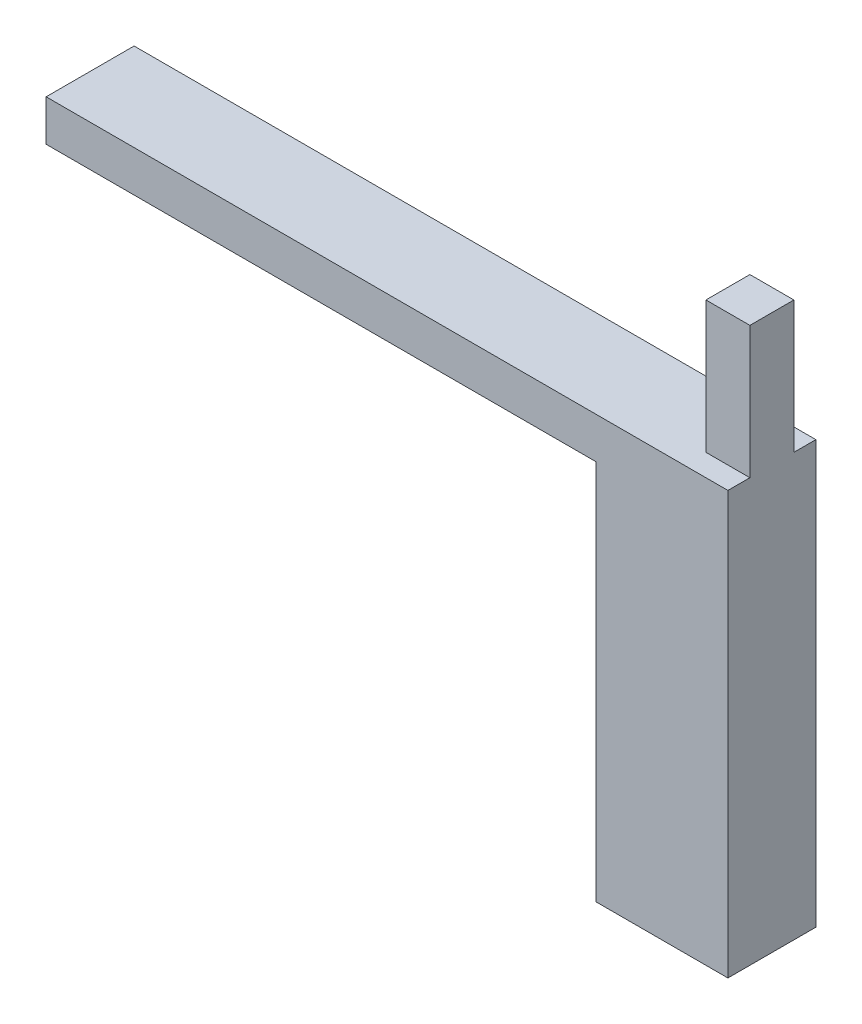
SolidWorks part; units mm, degrees
ref_plane "Front Plane" through (0, 0, 0) normal (0, 0, 1) x (1, 0, 0)
ref_plane "Top Plane" through (0, 0, 0) normal (0, 1, 0) x (1, 0, 0)
ref_plane "Right Plane" through (0, 0, 0) normal (1, 0, 0) x (0, 0, -1)
sketch "Sketch3" plane through (0, 0, 0) normal (0, 0, 1) x (1, 0, 0)
  line L0 (0, 0) -> (0, -5)
  line L1 (0, -5) -> (20, -5)
  line L2 (20, -5) -> (20, -25)
  line L3 (0, 0) -> (20, 0)
  line L4 (20, 0) -> (20, 30)
  line L5 (20, 30) -> (30, 30)
  line L6 (30, 30) -> (30, -25)
  line L7 (30, -25) -> (20, -25)
  dimension "D1" = 20
  dimension "D2" = 20
  dimension "D3" = 20
  dimension "D4" = 5
  dimension "D5" = 10
  dimension "D6" = 55
extrude "Boss-Extrude3" add sketch "Sketch3" along normal blind 10
sketch "Sketch5" plane through (0, 0, 10) normal (0, 0, 1) x (1, 0, 0)
  line L5 (0, 0) -> (30, 0)
  line L6 (0, 0) -> (0, -25)
  line L7 (0, -25) -> (30, -25)
  line L8 (30, 0) -> (30, -25)
extrude "Boss-Extrude5" add sketch "Sketch5" along normal blind 5
sketch "Sketch7" plane through (0, 0, 0) normal (0, 0, -1) x (-1, 0, 0)
  line L0 (-20, 0) -> (-30, 0)
  line L1 (-30, 0) -> (-30, -25)
  line L2 (-30, -25) -> (-20, -25)
  line L3 (-20, -25) -> (-20, -5)
  line L4 (-20, -5) -> (0, -5)
  line L5 (0, -5) -> (0, 0)
  line L6 (0, 0) -> (-20.7589, 0)
  line M8 (0, 0) -> (-20, 0)
  line M11 (-30, 30) -> (-30, -25)
  line M12 (-30, -25) -> (-20, -25)
  line M13 (-20, -25) -> (-20, -5)
  line M14 (-20, -5) -> (0, -5)
  line M15 (0, -5) -> (0, 0)
extrude "Boss-Extrude7" add sketch "Sketch7" along normal blind 5 contours L0 M8 M11 M12 M13 M14 M15 region at (20.7143, -9.6429, 0)
sketch "Sketch10" plane through (0, -25, 0) normal (0, -1, 0) x (1, 0, 0)
  line L0 (0, 10) -> (20, 10)
  line L1 (20, 10) -> (20, -5)
  line L2 (30, -5) -> (20, -5) construction
  line L3 (20, -5) -> (30, -5)
  line L4 (30, -5) -> (30, 15)
  line L5 (30, 15) -> (0, 15)
  line L6 (0, 15) -> (0, 10)
extrude "Boss-Extrude8" add sketch "Sketch10" along normal up to surface (71 mm away)
sketch "Sketch11" plane through (0, 0, 0) normal (-1, 0, 0) x (0, 0, 1)
  line L0 (15, 0) -> (15, -96) construction
  line L1 (-5, 0) -> (15, 0)
  line L2 (-5, 0) -> (-5, -5)
  line L3 (-5, -5) -> (10, -5)
  line L4 (15, 0) -> (15, -5)
  line L5 (10, -5) -> (10, -96) construction
  line L6 (15, 0) -> (10, 0)
  line L7 (15, 0) -> (15, -9.3485)
  line L8 (15, -9.3485) -> (10, -9.3485)
  line L9 (10, -4.5368) -> (10, -9.3485)
  line M2 (15, 0) -> (-5, 0)
  line M3 (-5, 0) -> (-5, -5)
  line M4 (-5, -5) -> (10, -5)
  line M5 (10, -5) -> (10, -96)
  line M7 (15, -96) -> (15, 0)
extrude "Boss-Extrude9" add sketch "Sketch11" along normal blind 125 contours L8 L1 M7 M2 M3 M4 M5 region at (0, -3.3348, 6.3395)
